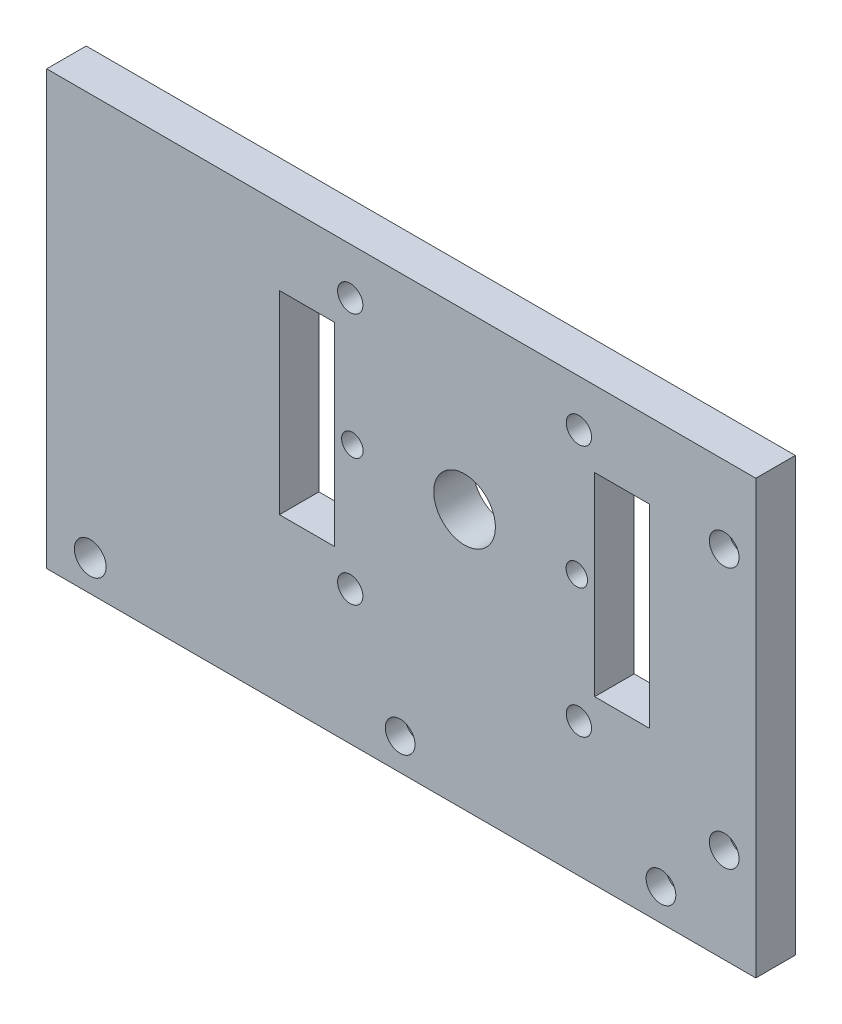
SolidWorks part; units mm, degrees
ref_plane "Front Plane" through (0, 0, 0) normal (0, 0, 1) x (1, 0, 0)
ref_plane "Top Plane" through (0, 0, 0) normal (0, 1, 0) x (1, 0, 0)
ref_plane "Right Plane" through (0, 0, 0) normal (1, 0, 0) x (0, 0, -1)
sketch "Brace Ref" plane through (0, 0, 0) normal (0, 0, 1) x (1, 0, 0)
  line B0 (-76.454, 5.6642) -> (-76.454, 10.0838)
  line B1 (-75.8588, 11.5206) -> (-73.7506, 13.6288)
  line B2 (-72.3138, 14.224) -> (-61.0148, 14.224)
  line B3 (-61.0148, 14.224) -> (-38.7641, 15.001)
  line B4 (-75.8588, 4.2274) -> (-73.7506, 2.1192)
  line B5 (-72.3138, 1.524) -> (-61.5696, 1.524)
  line B6 (-57.8366, 0) -> (-21.4114, 0)
  line B7 (-17.6784, 1.524) -> (-5.6642, 1.524)
  line B8 (-4.2274, 2.1192) -> (-2.1192, 4.2274)
  line B9 (-1.524, 5.6642) -> (-1.524, 17.6784)
  line B10 (0, 21.4114) -> (0, 57.8366)
  line B11 (-1.524, 61.5696) -> (-1.524, 72.3138)
  line B12 (-2.1192, 73.7506) -> (-4.2274, 75.8588)
  line B13 (-5.6642, 76.454) -> (-10.0838, 76.454)
  line B14 (-11.5206, 75.8588) -> (-13.6288, 73.7506)
  line B15 (-14.224, 72.3138) -> (-14.224, 61.0148)
  line B16 (-14.224, 61.0148) -> (-15.001, 38.7641)
  line B17 (-76.454, 0) -> (-76.454, 76.454) construction
  line B18 (-76.454, 0) -> (0, 0) construction
  line B19 (0, 0) -> (0, 76.454) construction
  line B20 (-76.454, 76.454) -> (0, 76.454) construction
  arc B21 (-76.454, 10.0838) -> (-75.8588, 11.5206) centre (-74.422, 10.0838) cw
  arc B22 (-73.7506, 13.6288) -> (-72.3138, 14.224) centre (-72.3138, 12.192) cw
  arc B23 (-38.7641, 15.001) -> (-27.0035, 18.4638) centre (-39.624, 39.624) ccw
  arc B24 (-27.0035, 18.4638) -> (-25.4333, 20.7849) centre (-28.6949, 21.2997) ccw
  arc B25 (-25.4333, 20.7849) -> (-20.7849, 25.4333) centre (-19.9136, 19.9136) cw
  arc B26 (-76.454, 5.6642) -> (-75.8588, 4.2274) centre (-74.422, 5.6642) ccw
  arc B27 (-73.7506, 2.1192) -> (-72.3138, 1.524) centre (-72.3138, 3.556) ccw
  arc B28 (-61.5696, 1.524) -> (-59.2587, 0.5806) centre (-61.5696, -1.778) cw
  arc B29 (-59.2587, 0.5806) -> (-57.8366, 0) centre (-57.8366, 2.032) ccw
  arc B30 (-21.4114, 0) -> (-19.9893, 0.5806) centre (-21.4114, 2.032) ccw
  arc B31 (-19.9893, 0.5806) -> (-17.6784, 1.524) centre (-17.6784, -1.778) cw
  arc B32 (-5.6642, 1.524) -> (-4.2274, 2.1192) centre (-5.6642, 3.556) ccw
  arc B33 (-2.1192, 4.2274) -> (-1.524, 5.6642) centre (-3.556, 5.6642) ccw
  arc B34 (-1.524, 17.6784) -> (-0.5806, 19.9893) centre (1.778, 17.6784) cw
  arc B35 (-0.5806, 19.9893) -> (0, 21.4114) centre (-2.032, 21.4114) ccw
  arc B36 (0, 57.8366) -> (-0.5806, 59.2587) centre (-2.032, 57.8366) ccw
  arc B37 (-0.5806, 59.2587) -> (-1.524, 61.5696) centre (1.778, 61.5696) cw
  arc B38 (-1.524, 72.3138) -> (-2.1192, 73.7506) centre (-3.556, 72.3138) ccw
  arc B39 (-4.2274, 75.8588) -> (-5.6642, 76.454) centre (-5.6642, 74.422) ccw
  arc B40 (-10.0838, 76.454) -> (-11.5206, 75.8588) centre (-10.0838, 74.422) ccw
  arc B41 (-13.6288, 73.7506) -> (-14.224, 72.3138) centre (-12.192, 72.3138) ccw
  arc B42 (-15.001, 38.7641) -> (-18.4638, 27.0035) centre (-39.624, 39.624) cw
  arc B43 (-18.4638, 27.0035) -> (-20.7849, 25.4333) centre (-21.2997, 28.6949) cw
  circle B44 centre (-70.104, 7.874) radius 4.3561
  circle B45 centre (-19.9136, 19.9136) radius 2.3813
  circle B46 centre (-7.874, 70.104) radius 4.3561
sketch_block_instance "Block1-1"
sketch_block "Block1" parameters "D1"=31.75, "D2"=30.48, "D3"=30.48, "D4"=31.75, "D5"=19.7104, "D6"=19.7104
sketch "Sketch5" plane through (0, 0, 0) normal (0, 0, 1) x (1, 0, 0)
  line L0 (-49.594, 49.547) -> (-49.594, 44.594) construction
  line L1 (-91.344, 72.344) -> (-2.794, 72.344)
  line L2 (-91.344, 72.344) -> (-91.344, 2.794)
  line L3 (-91.344, 2.794) -> (-2.794, 2.794)
  line L4 (-2.794, 72.344) -> (-2.794, 2.794)
  line L6 (-79.594, 60.594) -> (-19.594, 60.594) construction
  line L7 (-79.594, 60.594) -> (-79.594, 28.594) construction
  line L8 (-67.628, 44.594) -> (-49.594, 44.594) construction
  line L9 (-81.344, 62.344) -> (-17.844, 62.344) construction
  line L10 (-49.594, 44.594) -> (-31.56, 44.594) construction
  line L11 (-81.344, 62.344) -> (-81.344, 26.844) construction
  line L12 (-81.344, 26.844) -> (-17.844, 26.844) construction
  line L13 (-17.844, 62.344) -> (-17.844, 26.844) construction
  line L14 (-86.344, 67.344) -> (-12.844, 67.344) construction
  line L15 (-79.594, 28.594) -> (-19.594, 28.594) construction
  line L16 (-19.594, 60.594) -> (-19.594, 28.594) construction
  line L17 (-79.344, 60.194) -> (-70.494, 60.194)
  line L18 (-86.344, 67.344) -> (-86.344, 21.844) construction
  line L19 (-86.344, 21.844) -> (-12.844, 21.844) construction
  line L20 (-12.844, 67.344) -> (-12.844, 21.844) construction
  line L21 (-79.344, 60.194) -> (-79.344, 28.994)
  line L22 (-79.344, 28.994) -> (-70.494, 28.994)
  line L23 (-70.494, 60.194) -> (-70.494, 28.994)
  line L24 (-28.694, 60.194) -> (-19.844, 60.194)
  line L25 (-28.694, 60.194) -> (-28.694, 28.994)
  line L26 (-28.694, 28.994) -> (-19.844, 28.994)
  line L27 (-19.844, 60.194) -> (-19.844, 28.994)
  line L28 (-79.344, 60.194) -> (-79.594, 60.194) construction
  line L30 (-19.844, 60.194) -> (-19.594, 60.194) construction
  circle A7 centre (-49.594, 44.594) radius 4.953
  circle A10 centre (-19.9136, 19.9136) radius 3.683
  circle A14 centre (-59.944, 7.874) radius 1.5875
  circle A15 centre (-18.034, 7.874) radius 1.5875
  circle A16 centre (-7.874, 18.034) radius 1.5875
  circle A17 centre (-7.874, 59.944) radius 1.5875
  circle A18 centre (-19.9136, 19.9136) radius 2.3813 construction
  circle A19 centre (-67.628, 44.594) radius 1.6666 construction
  circle A21 centre (-31.56, 44.594) radius 1.6666 construction
  circle A22 centre (-39.594, 39.594) radius 0.5 construction
  circle A23 centre (-59.944, 7.874) radius 2.3876
  circle A24 centre (-18.034, 7.874) radius 2.3876
  circle A25 centre (-7.874, 59.944) radius 2.3876
  circle A26 centre (-7.874, 18.034) radius 2.3876
  circle A32 centre (-49.594, 44.594) radius 4.953
  circle A35 centre (-49.594, 44.594) radius 4.953
  circle A38 centre (-49.594, 44.594) radius 4.953
  point P6 (-49.594, 60.594)
  point P17 (-19.594, 44.594)
  point P25 (-49.594, 67.344)
  point P26 (-12.844, 44.594)
  point P39 (-70.494, 44.594)
  point P116 (-49.594, 44.594)
  dimension "D8" = 7.366
  dimension "D9" = 3.175
  dimension "D10" = 4.7752
  dimension "D2" = 9.906
  dimension "D22" = 3.3332
  dimension "D30" = 1
  dimension "D6" = 17.1196
  dimension "D7" = 17.1196
  dimension "D12" = 41.91
  dimension "D13" = 5.08
  dimension "D14" = 5.08
  dimension "D15" = 41.91
  dimension "D16" = 15.24
  dimension "D17" = 15.24
  dimension "D11" = 18.034
  dimension "D3" = 63.5
  dimension "D5" = 5
  dimension "D18" = 5
  dimension "D19" = 5
  dimension "D20" = 5
  dimension "D21" = 35.5
  dimension "D23" = 60
  dimension "D24" = 32
  dimension "D25" = 31.2
  dimension "D26" = 0.25
  dimension "D27" = 8.85
  dimension "D28" = 36.8
  dimension "D29" = 36.8
  dimension "D32" = 10
  dimension "D33" = 5
  dimension "D34" = 5
  dimension "D31" = 5
  dimension "D4" = 4
extrude "Boss-Extrude1" add sketch "Sketch5" along normal blind 6.35 contours L4 L1 L2 L3 A26 A25 A24 A23 A10 A7 L17 L23 L22 L21 L24 L27 L26 L25 | A25 A17 | A10 | A26 A16 | A24 A15 | A23 A14 region at (-47.302, 37.0786, 0) region at (-19.9136, 19.9136, 0) region at (-62.2641, 7.874, 0) region at (-20.3541, 7.874, 0) region at (-10.1941, 59.944, 0) region at (-10.1941, 18.034, 0)
hole_wizard "#8-32 Tapped Hole1" positions "3DSketch1" profile "Sketch6" tap size "#8-32" standard "ANSI Inch" end condition through all
sketch3d "3DSketch1"
  point P0 (-67.628, 44.594, 6.35)
  point P2 (-31.56, 44.594, 6.35)
sketch "Sketch6" plane through (-67.628, 44.594, 6.35) normal (1, 0, 0) x (0, -1, 0)
  line L0 (0, 0) -> (0, 6.35)
  line L1 (0, 6.35) -> (1.7272, 6.35)
  line L2 (1.7272, 6.35) -> (1.7272, 0)
  line L5 (1.7272, 0) -> (0, 0)
  line L11 (0, -6.35) -> (0, 107.95) construction
  dimension "Thru Tap Drill Dia." = 3.4544
  dimension "Thru Tap Drill Depth" = 6.35
cosmetic thread "Hole Thread1" parameters "D2"=4.1656
cosmetic thread "Hole Thread2" parameters "D2"=4.1656
extrude "Cut-Extrude2" cut sketch "Sketch5<3>" against normal blind 3.175 from surface contours A24 A15 | A26 A16 | A23 A14 | A25 A17 region at (-62.2641, 7.874, 0) region at (-20.3541, 7.874, 0) region at (-10.1941, 59.944, 0) region at (-10.1941, 18.034, 0) starting at face at (-65.9008, 44.594, 6.35)
sketch "Sketch5<3>" plane through (0, 0, 0) normal (0, 0, 1) x (1, 0, 0) same geometry as "Sketch5"
fillet "Fillet1" [suppressed] radius 6.35
sketch "Sketch8" plane through (0, 0, 0) normal (0, 0, 1) x (1, 0, 0)
  line L1 (-91.344, 2.794) -> (-116.744, 2.794)
  line L2 (-91.344, 2.794) -> (-91.344, 72.344)
  line L3 (-91.344, 72.344) -> (-116.744, 72.344)
  line L4 (-116.744, 2.794) -> (-116.744, 72.344)
  circle A0 centre (-109.744, 7.794) radius 1
  dimension "D2" = 2
  dimension "D1" = 25.4
  dimension "D3" = 5
  dimension "D4" = 7
extrude "Boss-Extrude2" add sketch "Sketch8" along normal up to surface (6.35 mm away) up to face at (-5.4864, 59.944, 6.35)
hole_wizard "1/4-20 Tapped Hole2" positions "3DSketch3" profile "Sketch10" tap size "1/4-20" standard "ANSI Inch" end condition through all
sketch3d "3DSketch3"
  line L0 (-109.744, 7.794, 6.35) -> (-109.744, 7.794, 0) construction
  point P0 (-109.744, 7.794, 6.35)
sketch "Sketch10" plane through (-109.744, 7.794, 6.35) normal (1, 0, 0) x (0, -1, 0)
  line L0 (0, 0) -> (0, 6.35)
  line L1 (0, 6.35) -> (2.5527, 6.35)
  line L2 (2.5527, 6.35) -> (2.5527, 0)
  line L5 (2.5527, 0) -> (0, 0)
  line L11 (0, -6.35) -> (0, 107.95) construction
  dimension "Thru Tap Drill Dia." = 5.1054
  dimension "Thru Tap Drill Depth" = 6.35
cosmetic thread "Hole Thread3" parameters "D2"=6.35
sketch "Sketch11" plane through (0, 0, 6.35) normal (0, 0, 1) x (1, 0, 0)
  line L0 (-2.794, 72.344) -> (-2.794, 2.794) construction
  line L1 (-67.969, 64.844) -> (-31.219, 64.844) construction
  line L2 (-67.969, 64.844) -> (-67.969, 24.344) construction
  line L3 (-67.969, 24.344) -> (-31.219, 24.344) construction
  line L4 (-31.219, 64.844) -> (-31.219, 24.344) construction
  line L5 (-116.744, 2.794) -> (-2.794, 2.794) construction
  circle A0 centre (-67.969, 64.844) radius 2.032
  circle A1 centre (-31.219, 64.844) radius 2.032
  circle A2 centre (-31.219, 24.344) radius 2.032
  circle A3 centre (-67.969, 24.344) radius 2.032
  dimension "D5" = 4.064
  dimension "D1" = 28.425
  dimension "D2" = 21.55
  dimension "D3" = 36.75
  dimension "D4" = 40.5
extrude "Cut-Extrude3" cut sketch "Sketch11" against normal through all both and the other way through all
equation "\"D18@Sketch5\"=\"D5@Sketch5\""
equation "\"D19@Sketch5\"=\"D18@Sketch5\""
equation "\"D20@Sketch5\"=\"D5@Sketch5\""
equation "\"D29@Sketch5\"=\"D28@Sketch5\""
